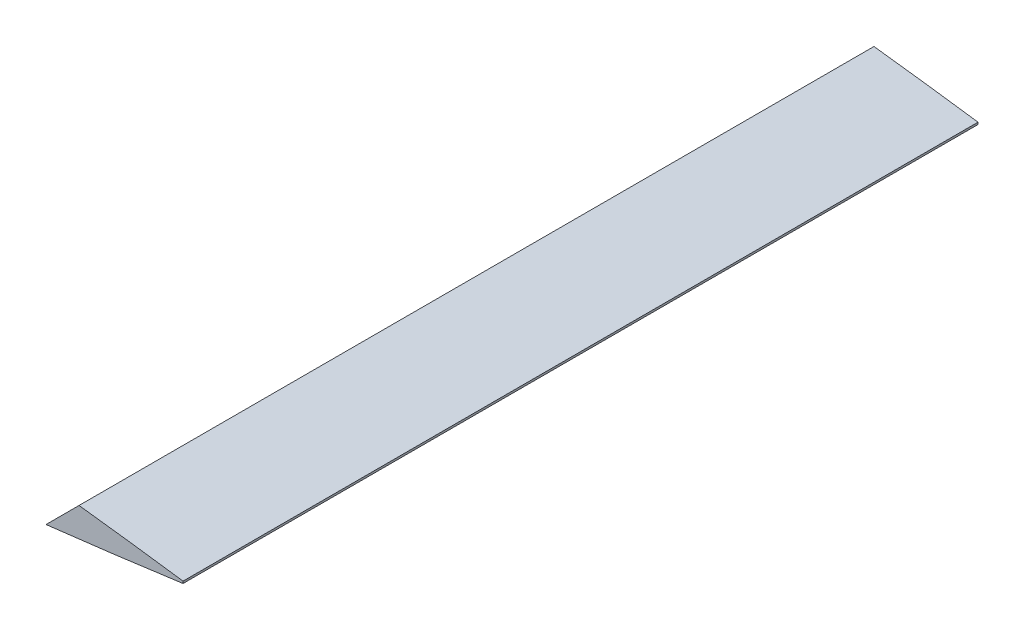
SolidWorks part; units mm, degrees
material "Balsa"
ref_plane "Front Plane" through (0, 0, 0) normal (0, 0, 1) x (1, 0, 0)
ref_plane "Top Plane" through (0, 0, 0) normal (0, 1, 0) x (1, 0, 0)
ref_plane "Right Plane" through (0, 0, 0) normal (1, 0, 0) x (0, 0, -1)
sketch "Sketch5" plane through (0, 0, 0) normal (0, 0, 1) x (1, 0, 0)
  line L1 (300, 0.378) -> (300, -0.378)
  spline S1 degree 3 poles (300, 0.378) (299.2704, 0.4794) (297.2347, 0.7625) (293.6597, 1.2577) (289.1124, 1.8742) (284.0808, 2.5445) (278.752, 3.2381) (273.2659, 3.9349) (267.706, 4.629) (262.1146, 5.3131) (256.5083, 5.9822) (250.8917, 6.638) (245.2696, 7.2818) (239.6473, 7.9122) (234.0251, 8.527) (228.3991, 9.1262) (222.7683, 9.7131) (217.1359, 10.2875) (211.5054, 10.8469) (205.8776, 11.3916) (200.2515, 11.9209) (194.6264, 12.4346) (189.0028, 12.9319) (183.3815, 13.4131) (177.7632, 13.8764) (172.1483, 14.3212) (166.5375, 14.7478) (160.9317, 15.1542) (155.3317, 15.5391) (149.7375, 15.9026) (144.1487, 16.2418) (138.5657, 16.5574) (132.9909, 16.8474) (127.4274, 17.1102) (121.8776, 17.3439) (116.3408, 17.5453) (110.8155, 17.7127) (105.3013, 17.8445) (99.8006, 17.9401) (94.3174, 17.9966) (88.8558, 18.0101) (83.4186, 17.9792) (78.0085, 17.8992) (72.6285, 17.767) (67.2827, 17.5794) (61.9774, 17.3315) (56.7207, 17.021) (51.5252, 16.641) (46.4082, 16.1902) (41.3942, 15.6617) (36.5157, 15.054) (31.819, 14.3656) (27.3662, 13.6035) (23.2352, 12.7826) (19.5026, 11.9203) (16.2183, 11.0446) (13.3892, 10.1751) (10.9849, 9.3335) (8.9616, 8.5221) (7.2673, 7.747) (5.8461, 7.0106) (4.6477, 6.3006) (3.6282, 5.6065) (2.7519, 4.9266) (2.0063, 4.2499) (1.3906, 3.5703) (0.901, 2.8909) (0.5293, 2.2202) (0.2605, 1.5665) (0.0857, 0.931) (-0.0035, 0.309) (-0.0035, -0.309) (0.0857, -0.931) (0.2605, -1.5665) (0.5293, -2.2202) (0.901, -2.8909) (1.3906, -3.5703) (2.0063, -4.2499) (2.7519, -4.9266) (3.6282, -5.6065) (4.6477, -6.3006) (5.8461, -7.0106) (7.2673, -7.747) (8.9616, -8.5221) (10.9849, -9.3335) (13.3892, -10.1751) (16.2183, -11.0446) (19.5026, -11.9203) (23.2352, -12.7826) (27.3661, -13.6036) (31.8191, -14.3651) (36.5156, -15.0541) (41.3942, -15.6616) (46.4082, -16.1902) (51.5252, -16.641) (56.7207, -17.021) (61.9774, -17.3315) (67.2827, -17.5794) (72.6285, -17.767) (78.0085, -17.8992) (83.4186, -17.9792) (88.8558, -18.0101) (94.3174, -17.9966) (99.8006, -17.9401) (105.3013, -17.8445) (110.8155, -17.7127) (116.3408, -17.5453) (121.8776, -17.3439) (127.4274, -17.1102) (132.9909, -16.8474) (138.5657, -16.5574) (144.1487, -16.2418) (149.7375, -15.9026) (155.3317, -15.5391) (160.9317, -15.1542) (166.5375, -14.7478) (172.1483, -14.3212) (177.7632, -13.8764) (183.3815, -13.4131) (189.0028, -12.9319) (194.6264, -12.4346) (200.2515, -11.9209) (205.8776, -11.3916) (211.5054, -10.8469) (217.1359, -10.2875) (222.7683, -9.7131) (228.3991, -9.1262) (234.0251, -8.527) (239.6473, -7.9122) (245.2696, -7.2818) (250.8917, -6.638) (256.5083, -5.9822) (262.1146, -5.3131) (267.706, -4.629) (273.2659, -3.9349) (278.752, -3.2381) (284.0808, -2.5445) (289.1124, -1.8742) (293.6597, -1.2577) (297.2347, -0.7625) (299.2704, -0.4794) (300, -0.378) knots 0 0 0 0 0.003612 0.010079 0.017699 0.026115 0.034971 0.04405 0.053234 0.062448 0.071674 0.080921 0.090178 0.099424 0.108664 0.117912 0.12717 0.136427 0.145675 0.154916 0.164153 0.173387 0.182616 0.191838 0.201053 0.21026 0.219459 0.228647 0.237822 0.246985 0.256137 0.265279 0.274407 0.283512 0.292592 0.301646 0.310682 0.319699 0.328695 0.33766 0.346589 0.355477 0.364323 0.373122 0.381868 0.390553 0.399166 0.40769 0.416098 0.424355 0.432412 0.440205 0.447631 0.454564 0.460855 0.466413 0.471229 0.475366 0.478901 0.481915 0.484499 0.486747 0.488741 0.490543 0.492182 0.493673 0.495032 0.496279 0.497425 0.49849 0.499503 0.500497 0.50151 0.502575 0.503721 0.504968 0.506327 0.507818 0.509457 0.511259 0.513253 0.515501 0.518085 0.521099 0.524634 0.528771 0.533587 0.539145 0.545436 0.55237 0.559795 0.567588 0.575645 0.583902 0.59231 0.600834 0.609447 0.618132 0.626878 0.635677 0.644523 0.653411 0.66234 0.671305 0.680301 0.689318 0.698354 0.707408 0.716488 0.725593 0.734721 0.743863 0.753015 0.762178 0.771353 0.780541 0.78974 0.798947 0.808162 0.817384 0.826613 0.835847 0.845084 0.854325 0.863573 0.87283 0.882088 0.891336 0.900576 0.909822 0.919079 0.928326 0.937552 0.946766 0.95595 0.965029 0.973885 0.982301 0.989921 0.996388 1 1 1 1
  dimension "Tail chord" = 300
extrude "Boss-Extrude1" add sketch "Sketch5" along normal blind 290
curve "Curve6"
  spline degree 3 poles (298.242, -0.1932, 0) (300.4407, 0, 0) (298.242, 0.1932, 0) (296.4349, 0.5367, 0) (292.0253, 1.0976, 0) (286.5771, 1.8592, 0) (279.4156, 2.8001, 0) (270.9173, 3.8949, 0) (261.066, 5.1159, 0) (250.0071, 6.4339, 0) (237.8495, 7.8187, 0) (224.7304, 9.2395, 0) (210.7923, 10.6647, 0) (196.1883, 12.0613, 0) (181.0783, 13.3946, 0) (165.6277, 14.6278, 0) (150.0058, 15.7225, 0) (134.3834, 16.6392, 0) (118.9317, 17.3387, 0) (103.8195, 17.7845, 0) (89.2123, 17.9443, 0) (75.2698, 17.7935, 0) (62.1444, 17.3161, 0) (49.9793, 16.5075, 0) (38.907, 15.374, 0) (29.0471, 13.9333, 0) (20.5034, 12.2128, 0) (13.3641, 10.246, 0) (7.6828, 8.0707, 0) (3.4992, 5.7028, 0) (0.7348, 3.1014, 0) (-0.3264, 0, 0) (0.7348, -3.1014, 0) (3.4992, -5.7028, 0) (7.6828, -8.0707, 0) (13.3641, -10.246, 0) (20.5034, -12.2128, 0) (29.0471, -13.9333, 0) (38.907, -15.374, 0) (49.9793, -16.5075, 0) (62.1444, -17.3161, 0) (75.2698, -17.7935, 0) (89.2123, -17.9443, 0) (103.8195, -17.7845, 0) (118.9317, -17.3387, 0) (134.3834, -16.6392, 0) (150.0058, -15.7225, 0) (165.6277, -14.6278, 0) (181.0783, -13.3946, 0) (196.1883, -12.0613, 0) (210.7923, -10.6647, 0) (224.7304, -9.2395, 0) (237.8495, -7.8187, 0) (250.0071, -6.4339, 0) (261.066, -5.1159, 0) (270.9173, -3.8949, 0) (279.4156, -2.8001, 0) (286.5771, -1.8592, 0) (292.0253, -1.0976, 0) (296.4349, -0.5367, 0) (298.242, -0.1932, 0) (300.4407, 0, 0) (298.242, 0.1932, 0) knots -0.012119 -0.005412 -0.001357 0 0.001357 0.005412 0.012119 0.021403 0.033159 0.047255 0.063534 0.081814 0.101892 0.123547 0.146538 0.170613 0.195504 0.220938 0.246636 0.272314 0.297694 0.3225 0.346466 0.36934 0.390884 0.410879 0.429129 0.445462 0.459736 0.471848 0.481751 0.489494 0.495334 0.5 0.504666 0.510506 0.518249 0.528152 0.540264 0.554538 0.570871 0.589121 0.609116 0.63066 0.653534 0.6775 0.702306 0.727686 0.753364 0.779062 0.804496 0.829387 0.853462 0.876453 0.898108 0.918186 0.936466 0.952745 0.966841 0.978597 0.987881 0.994588 0.998643 1 1.001357 1.005412 1.012119 periodic
sketch "Sketch8" plane through (0, 0, 0) normal (0, 1, 0) x (1, 0, 0)
  line L0 (0.0001, -290) -> (300, -290) construction
  line L1 (300, 0) -> (250, 0)
  line L2 (300, 0) -> (300, -290)
  line L3 (300, -290) -> (250, -290)
  line L4 (250, 0) -> (250, -290)
  dimension "Length of elevator" = 50
extrude "Cut-Extrude8" cut sketch "Sketch8" against normal blind 20 and the other way blind 20 flip side to cut
sketch "Sketch9" plane through (0, 0, 0) normal (0, 0, 1) x (1, 0, 0)
  line L0 (250, -6.7388) -> (280, 23.2612)
  line L1 (280, 23.2612) -> (250, 23.2612)
  line L2 (250, 23.2612) -> (250, -6.7388)
  dimension "D1" = 45
  dimension "D2" = 30
extrude "Cut-Extrude9" cut sketch "Sketch9" along normal blind 300
equation "\"Elevator\"= 50mm'Elevator cut"
equation "\"Length of elevator@Sketch8\" = \"Elevator\""
equation "\"Chord\"= 300mm'Tail chord"
equation "\"Tail chord@Sketch5\"=\"Chord\""
